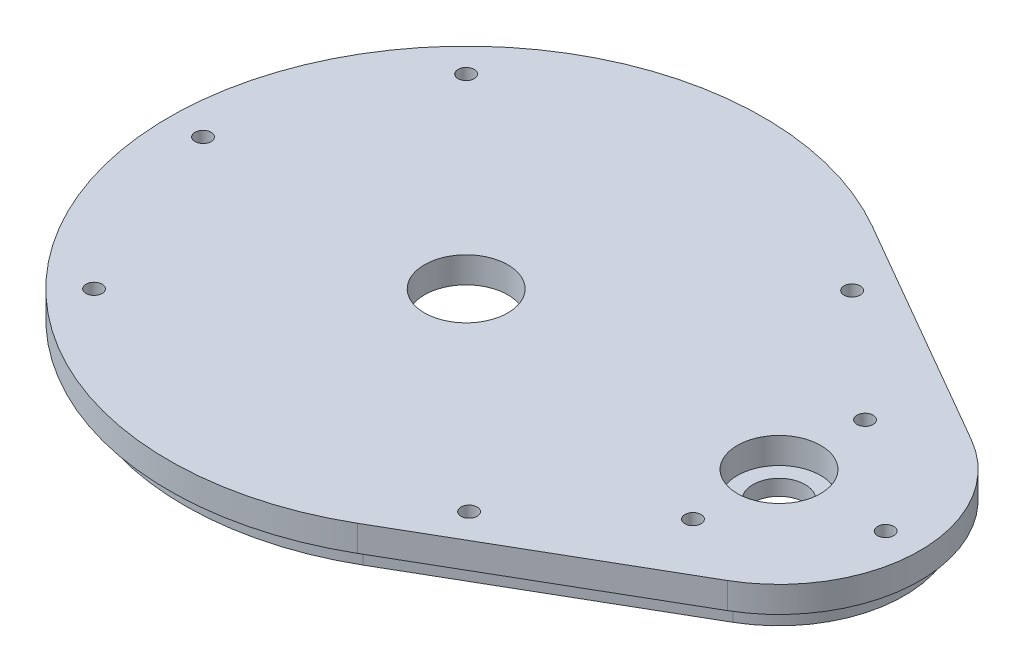
SolidWorks part; units mm, degrees
ref_plane "Front Plane" through (0, 0, 0) normal (0, 0, 1) x (1, 0, 0)
ref_plane "Top Plane" through (0, 0, 0) normal (0, 1, 0) x (1, 0, 0)
ref_plane "Right Plane" through (0, 0, 0) normal (1, 0, 0) x (0, 0, -1)
sketch "Sketch1" plane through (0, 0, 0) normal (0, 1, 0) x (1, 0, 0)
  line L8 (45, -16.5) -> (45, 16.5) construction
  line L9 (13.5, -49.3634) -> (58.5, -23.3827)
  line L10 (13.5, 49.3634) -> (58.5, 23.3827)
  circle A0 centre (-15, 0) radius 46.5 construction
  circle A1 centre (45, 0) radius 16.5 construction
  circle A2 centre (-15, 0) radius 8
  circle A3 centre (45, 0) radius 8
  circle A4 centre (45, 16.5) radius 1.55
  circle A5 centre (45, -16.5) radius 1.55
  circle A8 centre (-15, 0) radius 57 construction
  circle A9 centre (45, 0) radius 27 construction
  arc A12 (13.5, 49.3634) -> (13.5, -49.3634) centre (-15, 0) ccw
  arc A13 (58.5, 23.3827) -> (58.5, -23.3827) centre (45, 0) cw
  point P0 (0, 0)
  point P17 (45, 0)
  point P18 (45, 0)
extrude "Boss-Extrude1" add sketch "Sketch1" along normal blind 5
sketch "Sketch2" plane through (0, 0, 0) normal (0, -1, 0) x (1, 0, 0)
  circle A0 centre (45, 0) radius 5
  circle A1 centre (45, 0) radius 12
extrude "Boss-Extrude2" add sketch "Sketch2" along normal blind 3
sketch "Sketch4" plane through (0, 0, 0) normal (0, -1, 0) x (1, 0, 0)
  line L0 (12, 46.7654) -> (57, 20.7846)
  line L1 (12, -46.7654) -> (57, -20.7846)
  line L3 (11, -45.0333) -> (56, -19.0526)
  line L4 (11, 45.0333) -> (56, 19.0526)
  circle A0 centre (-15, 0) radius 54 construction
  circle A1 centre (45, 0) radius 24 construction
  arc A2 (12, 46.7654) -> (12, -46.7654) centre (-15, 0) ccw
  arc A3 (57, 20.7846) -> (57, -20.7846) centre (45, 0) cw
  circle A4 centre (-15, 0) radius 52 construction
  circle A5 centre (45, 0) radius 22 construction
  arc A8 (56, -19.0526) -> (56, 19.0526) centre (45, 0) ccw
  arc A9 (11, -45.0333) -> (11, 45.0333) centre (-15, 0) cw
extrude "Boss-Extrude3" add sketch "Sketch4" along normal blind 4
sketch "Sketch5" plane through (0, 5, 0) normal (0, 1, 0) x (1, 0, 0)
  line L0 (-67, 0) -> (-65.45, 0) construction
  line L1 (67, 0) -> (65.45, 0) construction
  line L2 (-51.9706, -36.9706) -> (21.9706, 36.9706) construction
  line L3 (-15, 0) -> (-51.7696, 36.7696) construction
  line L4 (-51.7696, -36.7696) -> (-50.6735, -35.6735) construction
  line L5 (23.0666, -38.0666) -> (22.2916, -36.7243) construction
  line L6 (11, 45.0333) -> (56, 19.0526) construction
  line L7 (-51.7696, 36.7696) -> (-50.6735, 35.6735) construction
  line L8 (11, -45.0333) -> (56, -19.0526) construction
  line L10 (23.0666, 38.0666) -> (22.2847, 36.7283) construction
  line L11 (-15, 0) -> (45, 0) construction
  arc A17 (11, 45.0333) -> (11, -45.0333) centre (-15, 0) ccw construction
  circle A18 centre (-65.45, 0) radius 1.55
  arc A20 (56, -19.0526) -> (56, 19.0526) centre (45, 0) ccw construction
  circle A21 centre (65.45, 0) radius 1.55
  circle A29 centre (-50.6735, -35.6735) radius 1.55
  circle A31 centre (-50.6735, 35.6735) radius 1.55
  circle A33 centre (22.2847, 36.7283) radius 1.55
  circle A35 centre (22.2916, -36.7243) radius 1.55
  point P39 (-15, 0)
  point P43 (0, 0)
  point P46 (0, 0)
extrude "Cut-Extrude1" cut sketch "Sketch5" against normal blind 5
